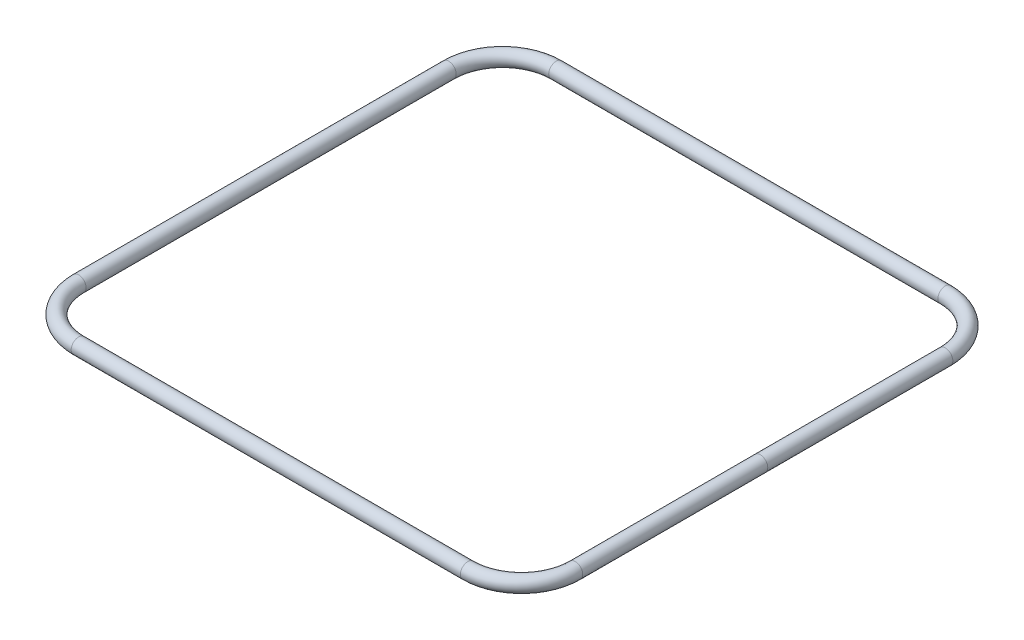
SolidWorks part; units mm, degrees
ref_plane "Front Plane" through (0, 0, 0) normal (0, 0, 1) x (1, 0, 0)
ref_plane "Top Plane" through (0, 0, 0) normal (0, 1, 0) x (1, 0, 0)
ref_plane "Right Plane" through (0, 0, 0) normal (1, 0, 0) x (0, 0, -1)
sketch "BaseDimensions" plane through (0, 0, 0) normal (0, 1, 0) x (1, 0, 0)
  line L0 (0, -63.5) -> (0, 63.5) construction
  line L1 (63.5, 0) -> (-63.5, 0) construction
  point P5 (0, 0)
  point P6 (0, 0)
  dimension "D1" = 127
  dimension "D2" = 127
sketch "O-RingPath" plane through (0, 0, 0) normal (0, 1, 0) x (1, 0, 0)
  line L0 (45.9922, -56.4388) -> (-45.9922, -56.4388)
  line L1 (58.6922, -43.7388) -> (58.6922, 43.7388)
  line L2 (0, 0) -> (0, -56.4388) construction
  line L3 (58.6922, 0) -> (0, 0) construction
  line L4 (-58.6922, -43.7388) -> (-58.6922, 43.7388)
  line L5 (45.9922, 56.4388) -> (-45.9922, 56.4388)
  arc A0 (45.9922, -56.4388) -> (58.6922, -43.7388) centre (45.9922, -43.7388) ccw
  arc A1 (-45.9922, -56.4388) -> (-58.6922, -43.7388) centre (-45.9922, -43.7388) cw
  arc A2 (-45.9922, 56.4388) -> (-58.6922, 43.7388) centre (-45.9922, 43.7388) ccw
  arc A3 (45.9922, 56.4388) -> (58.6922, 43.7388) centre (45.9922, 43.7388) cw
  point P17 (-58.6922, 0)
  dimension "D2" = 12.7
  dimension "D3" = 7.0612
sketch "O-RingProfile" plane through (0, 0, 0) normal (0, 0, 1) x (1, 0, 0)
  circle A0 centre (58.6922, 0) radius 1.7653
  dimension "D1" = 3.5306
sweep "Sweep2" add profiles "O-RingProfile" path "O-RingPath"
ref_plane "TopOfRing" through (0, 1.7653, 0) normal (0, 1, 0) x (1, 0, 0)
ref_plane "BottomOfRing" through (0, -1.7653, 0) normal (0, -1, 0) x (-1, 0, 0)
equation "\"D1@O-RingProfile\" = \"O-Ring_CS@BladderAssembly.SLDASM\""
equation "\"D1@BaseDimensions\"=\"BaseWidth@BladderAssembly.SLDASM\""
equation "\"D2@BaseDimensions\"=\"BaseLength@BladderAssembly.SLDASM\""
equation "\"O_Ring_Len\"= \"O-Ring_Len@BladderAssembly.SLDASM\""
equation "\"D1@O-RingPath\"=\"O_Ring_Len\""
